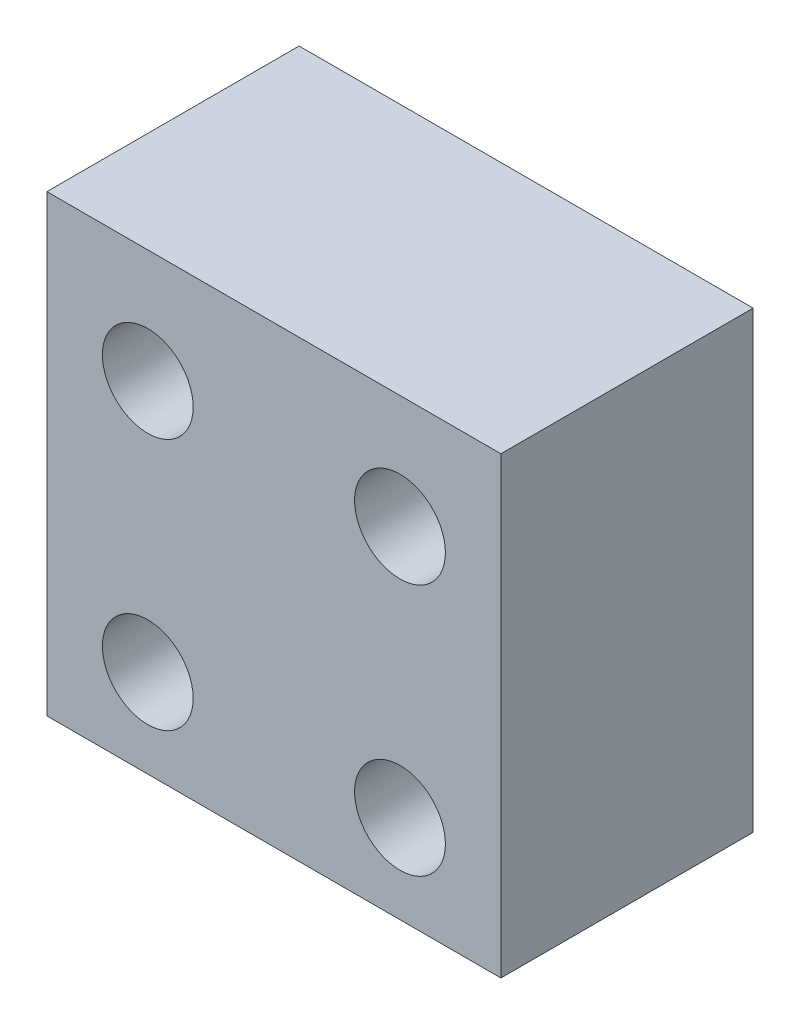
SolidWorks part; units mm, degrees
ref_plane "Front Plane" through (0, 0, 0) normal (0, 0, 1) x (1, 0, 0)
ref_plane "Top Plane" through (0, 0, 0) normal (0, 1, 0) x (1, 0, 0)
ref_plane "Right Plane" through (0, 0, 0) normal (1, 0, 0) x (0, 0, -1)
sketch "Sketch1" plane through (0, 0, 0) normal (0, 0, 1) x (1, 0, 0)
  line L0 (169, 104.999) -> (151, 104.999)
  line L8 (169, 86.999) -> (169, 104.999)
  line L10 (151, 104.999) -> (151, 86.999)
  line L11 (151, 86.999) -> (169, 86.999)
  dimension "D2" = 18
extrude "Boss-Extrude1" add sketch "Sketch1" along normal blind 10
sketch "Sketch2" plane through (0, 0, 10) normal (0, 0, 1) x (1, 0, 0)
  point P12 (155, 100.499)
  point P15 (155, 90.499)
  point P18 (165, 90.499)
  point P21 (165, 100.499)
hole_wizard "M3 Clearance Hole1" positions "Sketch2" profile "Sketch3" hole size "M3" standard "ANSI Metric" end condition through all
sketch "Sketch3" plane through (155, 100.499, 10) normal (1, 0, 0) x (0, -1, 0)
  line L0 (0, 0) -> (0, 10)
  line L1 (0, 10) -> (1.8, 10)
  line L2 (1.8, 10) -> (1.8, 0)
  line L5 (1.8, 0) -> (0, 0)
  line L11 (0, -6.35) -> (0, 107.95) construction
  dimension "Thru Hole Dia." = 3.6
  dimension "Thru Hole Depth" = 10
